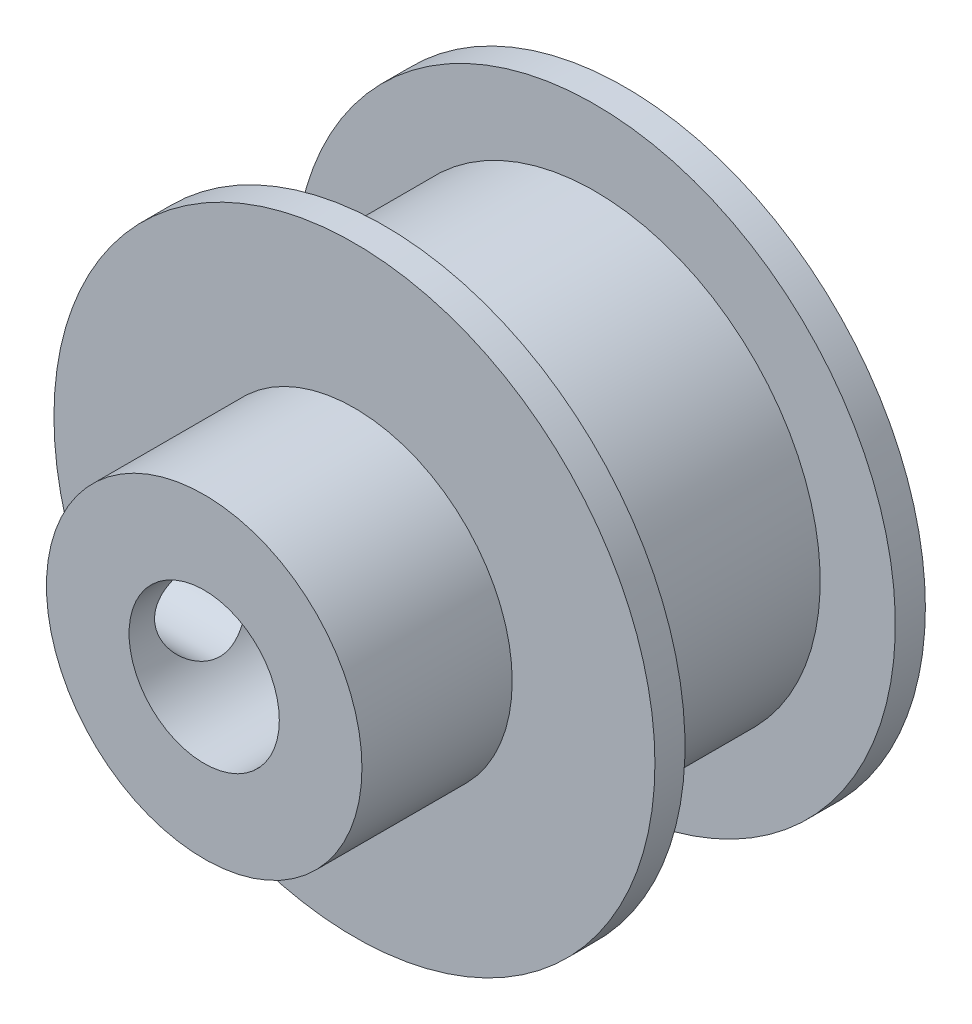
SolidWorks part; units mm, degrees
ref_plane "Plan de face" through (0, 0, 0) normal (0, 0, 1) x (1, 0, 0)
ref_plane "Plan de dessus" through (0, 0, 0) normal (0, 1, 0) x (1, 0, 0)
ref_plane "Plan de droite" through (0, 0, 0) normal (1, 0, 0) x (0, 0, -1)
sketch "Esquisse1" plane through (0, 0, 0) normal (0, 0, 1) x (1, 0, 0)
  circle A0 centre (0, 0) radius 10
  dimension "D1" = 20
extrude "Boss.-Extru.1" add sketch "Esquisse1" along normal blind 9
sketch "Esquisse2" plane through (0, 0, 9) normal (0, 0, 1) x (1, 0, 0)
  circle A0 centre (0, 0) radius 5.25
  dimension "D1" = 10.5
extrude "Boss.-Extru.2" add sketch "Esquisse2" along normal blind 5
sketch "Esquisse3" plane through (0, 0, 14) normal (0, 0, 1) x (1, 0, 0)
  circle A0 centre (0, 0) radius 2.5
  dimension "D1" = 5
extrude "Enlèv. mat.-Extru.1" cut sketch "Esquisse3" against normal through all
ref_axis "Axe1" through (0, 0, 0) along (0, 0, 1)
sketch "Esquisse4" plane through (0, 0, 0) normal (1, 0, 0) x (0, 0, -1)
  line L0 (0, 10) -> (-9, 10) construction
  line L1 (-8, 10) -> (-1, 10)
  line L2 (-8, 10) -> (-8, 7.5)
  line L3 (-8, 7.5) -> (-1, 7.5)
  line L4 (-1, 10) -> (-1, 7.5)
  line L5 (-9, 10) -> (-9, -10) construction
  line L6 (0, -10) -> (0, 10) construction
  dimension "D1" = 1
  dimension "D2" = 1
  dimension "D3" = 2.5
revolve "Enlèvement de matière-Révolution1" cut sketch "Esquisse4" angle 360 about axis through (0, 0, 0) along (0, 0, 1)
hole_wizard "Dégagement M31" positions "Esquisse3D1" profile "Esquisse5" hole size "M3" standard "Ansi Metric" end condition up to next
sketch3d "Esquisse3D1"
  line L0 (0, 0, 9) -> (0, 0, 14.1032) construction
  line L1 (0, 0, 14) -> (0, 0, 9) construction
  line L2 (0, 0, 0) -> (0, 0, 14) construction
  line L4 (0, 0, 11.5516) -> (-9.9534, 0, 11.5516) construction
  point P0 (-5.25, 0, 11.5516)
sketch "Esquisse5" plane through (-5.25, 0, 11.5516) normal (0, 1, 0) x (0, 0, 1)
  line L0 (0, 0) -> (0, 2.75)
  line L1 (0, 2.75) -> (1.6, 2.75)
  line L2 (1.6, 2.75) -> (1.6, 0.025)
  line L3 (1.6, 0.025) -> (1.625, 0)
  line L5 (1.625, 0) -> (0, 0)
  line L6 (-1.6, 0.025) -> (-1.625, 0) construction
  line L11 (0, -6.35) -> (0, 107.95) construction
  dimension "Diamètre du perçage jusqu'au prochain" = 3.2
  dimension "Profondeur du perçage jusqu'au prochain" = 2.75
  dimension "Diamètre du fraisage entrant" = 3.25
  dimension "Angle du fraisage entrant" = 90
